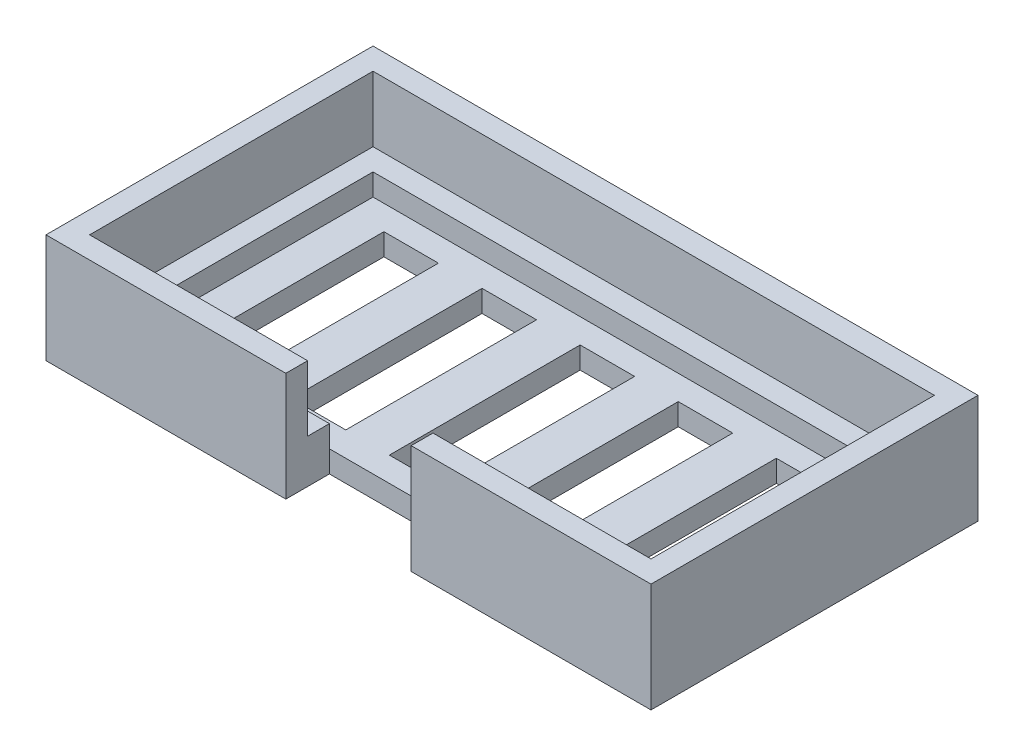
SolidWorks part; units mm, degrees
ref_plane "Front Plane" through (0, 0, 0) normal (0, 0, 1) x (1, 0, 0)
ref_plane "Top Plane" through (0, 0, 0) normal (0, 1, 0) x (1, 0, 0)
ref_plane "Right Plane" through (0, 0, 0) normal (1, 0, 0) x (0, 0, -1)
sketch "Sketch1" plane through (0, 0, 0) normal (0, 1, 0) x (1, 0, 0)
  line L0 (27.75, 15) -> (-27.75, 15)
  line L1 (25.75, -13) -> (5.75, -13)
  line L2 (25.75, -13) -> (25.75, 13)
  line L3 (25.75, 13) -> (-25.75, 13)
  line L4 (-25.75, -13) -> (-25.75, 13)
  line L5 (25.75, -13) -> (-25.75, 13) construction
  line L6 (25.75, 13) -> (-25.75, -13) construction
  line L7 (-27.75, -15) -> (-27.75, 15)
  line L8 (27.75, -15) -> (5.75, -15)
  line L9 (27.75, -15) -> (27.75, 15)
  line L10 (23.75, 11) -> (-23.75, 11)
  line L11 (-23.75, -11) -> (-23.75, 11)
  line L12 (23.75, -11) -> (5.75, -11)
  line L13 (23.75, -11) -> (23.75, 11)
  line L14 (0, 15) -> (0, -15) construction
  line L15 (-5.75, -11) -> (-23.75, -11)
  line L16 (-5.75, -11) -> (5.75, -11)
  line L17 (5.75, -15) -> (5.75, -11)
  line L18 (-5.75, -15) -> (-27.75, -15)
  line L19 (-5.75, -15) -> (-5.75, -11)
  line L20 (5.75, -15) -> (-5.75, -11) construction
  line L21 (5.75, -11) -> (-5.75, -15) construction
  line L22 (-5.75, -13) -> (-25.75, -13)
  line L23 (23.75, -11) -> (-23.75, -11) construction
  line L25 (25.75, -13) -> (-25.75, -13) construction
  line L26 (27.75, -15) -> (-27.75, -15) construction
  point P0 (0, 0)
  point P16 (0, -13)
  dimension "D1" = 51.5
  dimension "D2" = 26
  dimension "D5" = 11.5
  dimension "D3" = 2
  dimension "D4" = 2
extrude "Boss-Extrude1" add sketch "Sketch1" along normal blind 4 contours L4 L1 L2 L3 L13 L12 L11 L10 region at (6.3269, 0, 12)
extrude "Boss-Extrude3" add sketch "Sketch1<4>" along normal blind 10 contours L8 L9 L0 L7 L1 L4 L3 L2 region at (27.1191, 0, 0)
sketch "Sketch1<4>" plane through (0, 0, 0) normal (0, 1, 0) x (1, 0, 0) same geometry as "Sketch1"
sketch "Sketch2" plane through (0, 2, 0) normal (0, 1, 0) x (1, 0, 0)
  line L0 (6.5, -8.75) -> (6.5, 8.75)
  line L1 (2.5, -8.75) -> (-2.5, -8.75)
  line L2 (2.5, -8.75) -> (2.5, 8.75)
  line L3 (2.5, 8.75) -> (-2.5, 8.75)
  line L4 (-2.5, -8.75) -> (-2.5, 8.75)
  line L5 (2.5, -8.75) -> (-2.5, 8.75) construction
  line L6 (2.5, 8.75) -> (-2.5, -8.75) construction
  line L7 (11.5, 8.75) -> (6.5, 8.75)
  line L8 (11.5, -8.75) -> (11.5, 8.75)
  line L9 (11.5, -8.75) -> (6.5, -8.75)
  line L10 (15.5, -8.75) -> (15.5, 8.75)
  line L11 (20.5, 8.75) -> (15.5, 8.75)
  line L12 (20.5, -8.75) -> (20.5, 8.75)
  line L13 (20.5, -8.75) -> (15.5, -8.75)
  line L14 (-2.5, -8.75) -> (6.5, -8.75) construction
  line L15 (-11.5, -8.75) -> (-11.5, 8.75)
  line L16 (-6.5, 8.75) -> (-11.5, 8.75)
  line L17 (-6.5, -8.75) -> (-6.5, 8.75)
  line L18 (-6.5, -8.75) -> (-11.5, -8.75)
  line L19 (-20.5, -8.75) -> (-20.5, 8.75)
  line L20 (-15.5, 8.75) -> (-20.5, 8.75)
  line L21 (-15.5, -8.75) -> (-15.5, 8.75)
  line L22 (-15.5, -8.75) -> (-20.5, -8.75)
  line L23 (-2.5, -8.75) -> (-11.5, -8.75) construction
  point P0 (0, 0)
  dimension "D1" = 5
  dimension "D2" = 17.5
  dimension "D4" = 9
  dimension "D6" = 9
  dimension "D3" = 3
  dimension "D5" = 3
extrude "Boss-Extrude4" add sketch "Sketch1<6>" along normal blind 2 contours L15 L16 L12 L13 L10 L11 region at (0, 0, 0)
sketch "Sketch1<6>" plane through (0, 0, 0) normal (0, 1, 0) x (1, 0, 0) same geometry as "Sketch1"
extrude "Cut-Extrude2" cut sketch "Sketch2" against normal blind 2
